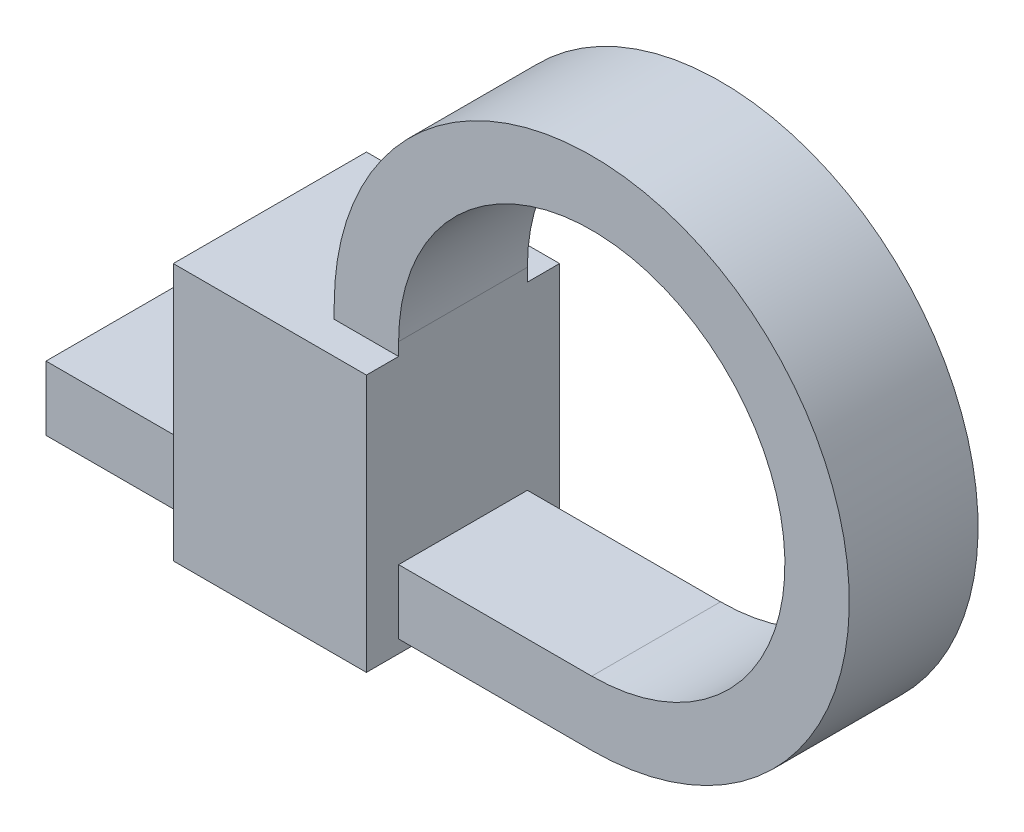
SolidWorks part; units mm, degrees
ref_plane "Front Plane" through (0, 0, 0) normal (0, 0, 1) x (1, 0, 0)
ref_plane "Top Plane" through (0, 0, 0) normal (0, 1, 0) x (1, 0, 0)
ref_plane "Right Plane" through (0, 0, 0) normal (1, 0, 0) x (0, 0, -1)
sketch "Sketch1" plane through (0, 0, 0) normal (0, 1, 0) x (1, 0, 0)
  line L0 (-10, -10) -> (10, 10) construction
  line L1 (-10, -10) -> (10, -10)
  line L2 (-10, -10) -> (-10, 10)
  line L3 (-10, 10) -> (10, 10)
  line L4 (10, -10) -> (10, 10)
  dimension "D1" = 20
extrude "Extrude1" add sketch "Sketch1" along normal blind 1
sketch "Sketch2" plane through (0, 1, 0) normal (0, 1, 0) x (-1, 0, 0)
  line L4 (10, -10) -> (10, 10)
  line L5 (10, 10) -> (-10, 10)
  line L6 (-10, 10) -> (-10, -10)
  line L7 (-10, -10) -> (10, -10)
  line L8 (10, -10) -> (10, 10)
  line L9 (10, 10) -> (-10, 10)
  line L10 (-10, 10) -> (-10, -10)
  line L11 (-10, -10) -> (10, -10)
  dimension "D1" = 0
extrude "Extrude2" add sketch "Sketch2" along normal blind 1.5 draft 75
sketch "Sketch3" plane through (0, 0, 0) normal (0, 0, 1) x (1, 0, 0)
  line L1 (-4.4019, 2.5) -> (-1.4019, 2.5)
  line L2 (-4.4019, 2.5) -> (-4.4019, 6.5)
  line L3 (-4.4019, 6.5) -> (-1.4019, 6.5)
  line L4 (-1.4019, 2.5) -> (-1.4019, 6.5)
  dimension "D1" = 4
  dimension "D2" = 3
extrude "Extrude3" add sketch "Sketch3" along normal mid plane 4
sketch "Sketch4" plane through (0, 0, 0) normal (0, 0, 1) x (1, 0, 0)
  line L0 (-1.4019, 2.5) -> (-1.4019, 6.5) construction
  line L1 (1.5981, 3.7) -> (-6.8786, 3.7)
  line L2 (-4.4019, 2.5) -> (4.4019, 2.5) construction
  line L3 (-1.4019, 6.5) -> (-1.4019, 6.7)
  arc A0 (-1.4019, 6.7) -> (1.5981, 3.7) centre (1.5981, 6.7) cw
  dimension "D2" = 6
  dimension "D1" = 1.2
extrude "Extrude-Thin1" add sketch "Sketch4" along normal mid plane 3 thin thin type one direction reverse wall 1
other "Move Face1" flip direction yes face at (-3.2769, 5, 2) face at (0.1543, 5.9562, 1.5) face at (-5.6403, 3.2, 1.5) offset 1 parameters "D1"=1
sketch "FilterSketch" plane through (0, 0, 0) normal (0, 0, 1) x (1, 0, 0)
  circle A0 centre (1.5981, 6.7) radius 3
  circle A1 centre (1.5981, 6.7) radius 3
  circle A2 centre (1.5981, 6.7) radius 0.5
  dimension "OuterDiameter" = 6
  dimension "NominalDiameter" = 6
  dimension "InnerDiameter" = 1
sketch3d "3DSketch1"
  arc A1 (-1.4019, 6.7, 0.5) -> (1.5981, 3.7, 0.5) centre (1.5981, 6.7, 0.5) ccw construction
  arc A2 (-1.4019, 6.7, -1.5) -> (1.5981, 3.7, -1.5) centre (1.5981, 6.7, -1.5) ccw construction
  point P0 (1.5981, 6.7, 0.5)
  point P1 (1.5981, 6.7, -1.5)
  point P5 (1.5981, 6.7, -4.5)
  point P9 (1.5981, 6.7, -2.5)
other "RPoint1"
ref_axis "Axis1" through (1.5981, 6.7, -4.5) along (0, 0, 1)
other "RPoint2"
ref_axis "Axis2" through (1.5981, 6.7, 3.5) along (0, 0, -1)
ref_axis "Clip Axis" through (1.5981, 6.7, 4.3871) along (0, 0, -1)
ref_axis "Axis of Rotation" through (0, 11.11, 0) along (0, -1, 0)
sketch "Sketch5" plane through (0, 2.5, 0) normal (0, 1, 0) x (1, 0, 0)
  line L1 (13.4512, 10.9981) -> (-12.8708, 10.9981)
  line L2 (13.4512, 10.9981) -> (13.4512, -13.1438)
  line L3 (13.4512, -13.1438) -> (-12.8708, -13.1438)
  line L4 (-12.8708, 10.9981) -> (-12.8708, -13.1438)
extrude "Cut-Extrude1" cut sketch "Sketch5" against normal blind 10
